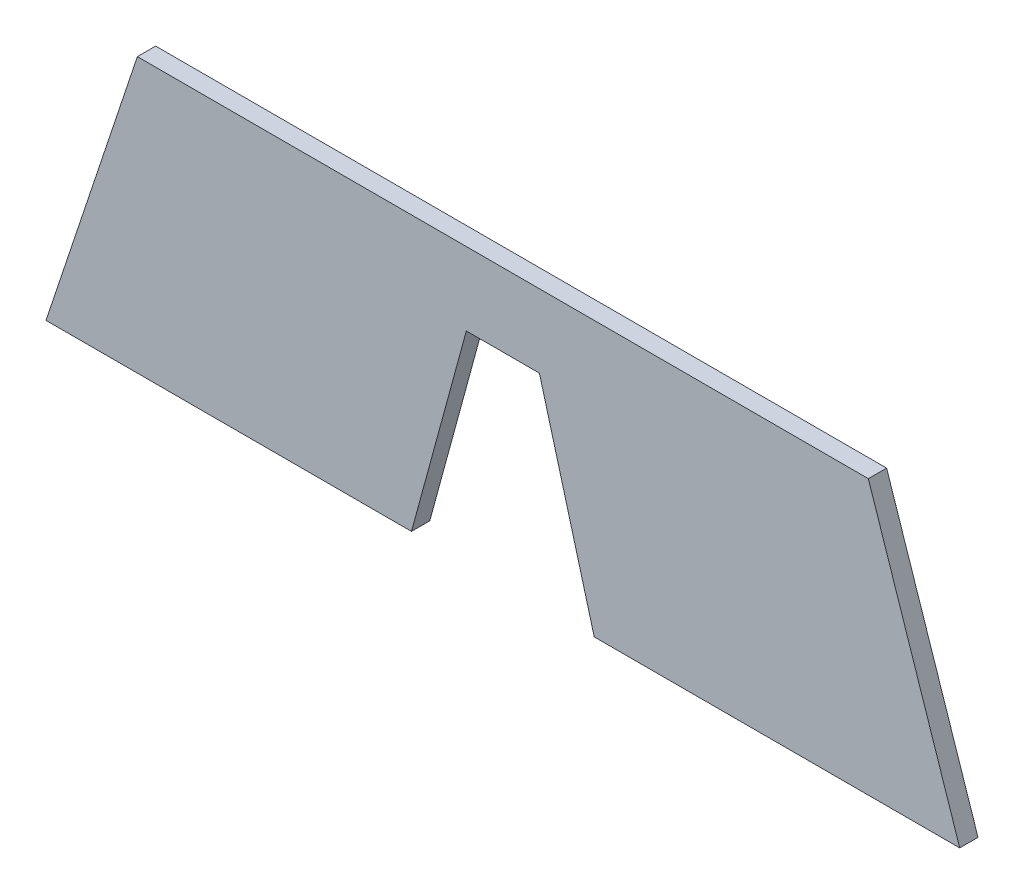
SolidWorks part; units mm, degrees
ref_plane "Front Plane" through (0, 0, 0) normal (0, 0, 1) x (1, 0, 0)
ref_plane "Top Plane" through (0, 0, 0) normal (0, 1, 0) x (1, 0, 0)
ref_plane "Right Plane" through (0, 0, 0) normal (1, 0, 0) x (0, 0, -1)
sketch "Sketch1" plane through (0, 0, 0) normal (0, 0, 1) x (1, 0, 0)
  line L0 (-28.872, 0) -> (51.128, 0)
  line L1 (-28.872, 0) -> (-38.872, -30)
  line L2 (-38.872, -30) -> (61.128, -30)
  line L3 (61.128, -30) -> (51.128, 0)
  line L5 (1.128, -30) -> (7.128, -8)
  line L6 (7.128, -8) -> (15.128, -8)
  line L7 (15.128, -8) -> (21.128, -30)
  point P9 (7.5914, -10.4244)
  point P12 (1.128, -27.9063)
  point P13 (0, 0)
  point P14 (0, 0)
  dimension "D1" = 80
  dimension "D2" = 100
  dimension "D3" = 30
  dimension "D5" = 8
  dimension "D6" = 20
  dimension "D9" = 8
extrude "Boss-Extrude1" add sketch "Sketch1" along normal blind 2 contours L6 L7 L2 L3 L0 L1 L5 region at (11.128, -1.044, 0)
